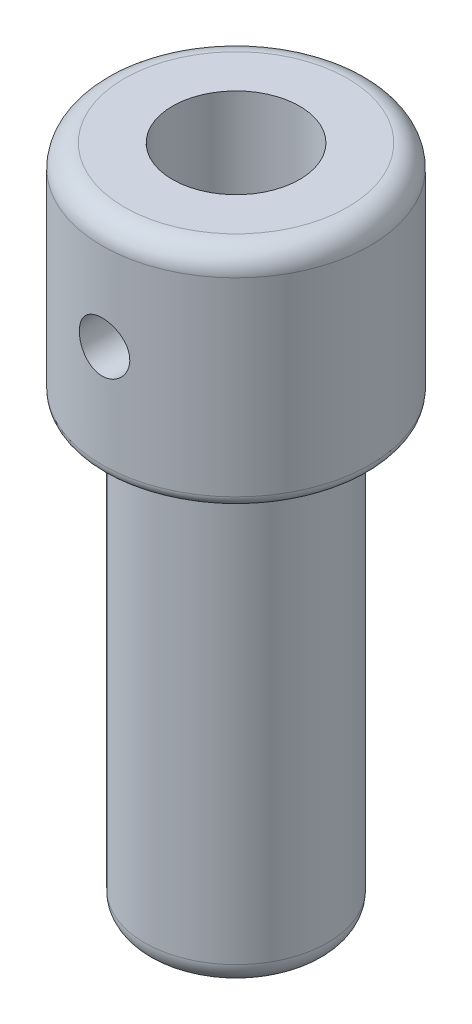
SolidWorks part; units mm, degrees
ref_plane "Front Plane" through (0, 0, 0) normal (0, 0, 1) x (1, 0, 0)
ref_plane "Top Plane" through (0, 0, 0) normal (0, 1, 0) x (1, 0, 0)
ref_plane "Right Plane" through (0, 0, 0) normal (1, 0, 0) x (0, 0, -1)
sketch "Sketch1" plane through (0, 0, 0) normal (0, 0, 1) x (1, 0, 0)
  line L0 (0, 27.8834) -> (0, -14.808) construction
  line L1 (2.85, 19.1329) -> (5, 19.1329)
  line L2 (6, 18.1329) -> (6, 9.6329)
  line L3 (5.5, 9.1329) -> (5.1, 9.1329)
  line L4 (4.1, 8.1329) -> (4.1, -9.8671)
  line L5 (3.1, -10.8671) -> (2.85, -10.8671)
  line L6 (2.85, 19.1329) -> (2.85, -10.8671)
  arc A0 (4.1, 8.1329) -> (5.1, 9.1329) centre (5.1, 8.1329) cw
  arc A1 (6, 9.6329) -> (5.5, 9.1329) centre (5.5, 9.6329) cw
  arc A2 (6, 18.1329) -> (5, 19.1329) centre (5, 18.1329) ccw
  arc A3 (4.1, -9.8671) -> (3.1, -10.8671) centre (3.1, -9.8671) cw
  point P11 (4.1, 9.1329)
  point P14 (6, 9.1329)
  point P17 (6, 19.1329)
  point P20 (4.1, -10.8671)
  dimension "D6" = 1
  dimension "D7" = 0.5
  dimension "D8" = 1
  dimension "D9" = 1
  dimension "D1" = 6
  dimension "D2" = 4.1
  dimension "D3" = 10
  dimension "D4" = 20
  dimension "D5" = 2.85
revolve "Revolve1" add sketch "Sketch1" angle 360 about L0
sketch "Sketch2" plane through (0, 0, 0) normal (0, 0, 1) x (1, 0, 0)
  circle A0 centre (0, 14.208) radius 1.1303
  dimension "D1" = 2.2606
extrude "Cut-Extrude1" cut sketch "Sketch2" against normal blind 10 and the other way blind 10
